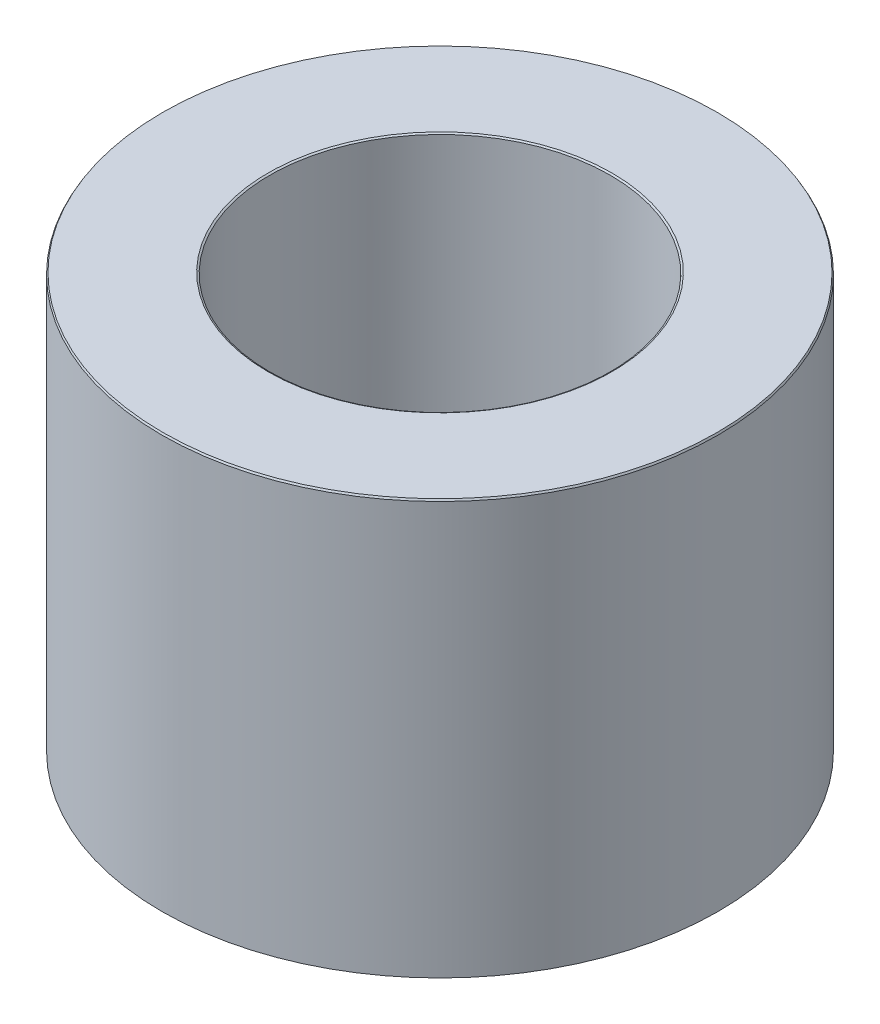
SolidWorks part; units mm, degrees
ref_plane "Front Plane" through (0, 0, 0) normal (0, 0, 1) x (1, 0, 0)
ref_plane "Top Plane" through (0, 0, 0) normal (0, 1, 0) x (1, 0, 0)
ref_plane "Right Plane" through (0, 0, 0) normal (1, 0, 0) x (0, 0, -1)
sketch "Sketch1" plane through (0, 0, 0) normal (0, 1, 0) x (1, 0, 0)
  circle A0 centre (0, 0) radius 32.5
  dimension "SLEEVE_OD" = 65
extrude "Boss-Extrude1" add sketch "Sketch1" along normal blind 48.5175
sketch "Sketch2" plane through (0, 0, 0) normal (0, 1, 0) x (1, 0, 0)
  circle A0 centre (0, 0) radius 19.8949
  dimension "BORE_D" = 39.7898
extrude "Cut-Extrude1" cut sketch "Sketch2" along normal through all
chamfer "Chamfer1" distance 0.2032 angle 30 4 edges at (0, 48.5175, 19.8949) (0, 0, 19.8949) (0, 0, 32.5) (0, 48.5175, 32.5) first distance on face at (0, 48.5175, 19.8949) first distance on face at (0, 0, 19.8949) first distance on face at (0, 48.5175, 32.5)
